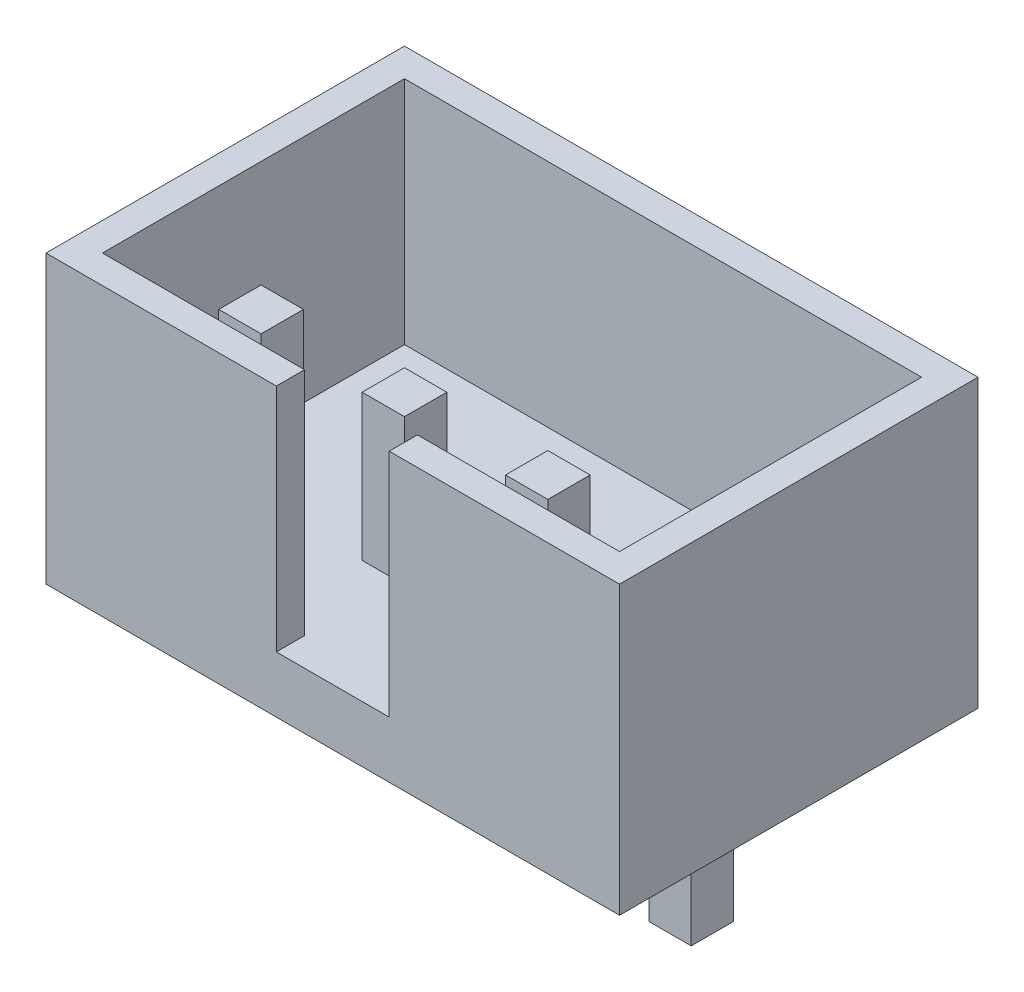
SolidWorks part; units mm, degrees
ref_plane "前视基准面" through (0, 0, 0) normal (0, 0, 1) x (1, 0, 0)
ref_plane "上视基准面" through (0, 0, 0) normal (0, 1, 0) x (1, 0, 0)
ref_plane "右视基准面" through (0, 0, 0) normal (1, 0, 0) x (0, 0, -1)
sketch "草图1" plane through (0, 0, 0) normal (0, 1, 0) x (1, 0, 0)
  line L0 (0, 7.1914) -> (0, -5.4429) construction
  line L1 (-5.08, 3.175) -> (5.08, 3.175)
  line L2 (-5.08, 3.175) -> (-5.08, -3.175)
  line L3 (-5.08, -3.175) -> (5.08, -3.175)
  line L4 (5.08, 3.175) -> (5.08, -3.175)
  line L5 (-10.6234, 0) -> (16.1963, 0) construction
  dimension "D1" = 10.16
  dimension "D2" = 6.35
extrude "拉伸1" add sketch "草图1" along normal blind 5.08
sketch "草图2" plane through (0, 5.08, 0) normal (0, 1, 0) x (-1, 0, 0)
  line L8 (4.58, -2.675) -> (4.58, 2.675)
  line L9 (4.58, 2.675) -> (-4.58, 2.675)
  line L10 (-4.58, 2.675) -> (-4.58, -2.675)
  line L11 (-4.58, -2.675) -> (4.58, -2.675)
  line L12 (4.58, -2.675) -> (4.58, 2.675)
  line L13 (4.58, 2.675) -> (-4.58, 2.675)
  line L14 (-4.58, 2.675) -> (-4.58, -2.675)
  line L15 (-4.58, -2.675) -> (4.58, -2.675)
  dimension "D1" = 0.5
extrude "切除-拉伸1" cut sketch "草图2" against normal offset from surface (4.08 mm away) 1 up to face at (0, 0, 0)
sketch "草图3" plane through (0, 0, 3.175) normal (0, 0, 1) x (1, 0, 0)
  line L0 (-5.08, 5.08) -> (5.08, 5.08) construction
  line L1 (-1, 5.08) -> (1, 5.08)
  line L2 (-1, 5.08) -> (-1, 1)
  line L3 (-1, 1) -> (1, 1)
  line L4 (1, 5.08) -> (1, 1)
  line L5 (4.58, 1) -> (-4.58, 1) construction
  line L6 (0, -1.5083) -> (0, 12.2426) construction
  dimension "D1" = 2
extrude "切除-拉伸2" cut sketch "草图3" against normal blind 1
sketch "草图4" plane through (0, 0, 0) normal (0, -1, 0) x (1, 0, 0)
  line L0 (7.6775, 0.635) -> (-8.5467, 0.635) construction
  line L1 (-5.08, 3.175) -> (5.08, 3.175) construction
  line L2 (0, -3.6953) -> (0, 4.0669) construction
  line L3 (-1.27, 2.1009) -> (-1.27, -0.7012) construction
  line L4 (-1.645, 1.01) -> (-0.895, 1.01)
  line L5 (-1.645, 1.01) -> (-1.645, 0.26)
  line L6 (-1.645, 0.26) -> (-0.895, 0.26)
  line L7 (-0.895, 1.01) -> (-0.895, 0.26)
  line L8 (0.895, 1.01) -> (1.645, 1.01)
  line L9 (0.895, 1.01) -> (0.895, 0.26)
  line L10 (0.895, 0.26) -> (1.645, 0.26)
  line L11 (1.645, 1.01) -> (1.645, 0.26)
  line L12 (3.435, 1.01) -> (4.185, 1.01)
  line L13 (3.435, 1.01) -> (3.435, 0.26)
  line L14 (3.435, 0.26) -> (4.185, 0.26)
  line L15 (4.185, 1.01) -> (4.185, 0.26)
  line L16 (-4.185, 1.01) -> (-3.435, 1.01)
  line L17 (-4.185, 1.01) -> (-4.185, 0.26)
  line L18 (-4.185, 0.26) -> (-3.435, 0.26)
  line L19 (-3.435, 1.01) -> (-3.435, 0.26)
  dimension "D1" = 2.54
  dimension "D2" = 0.75
  dimension "D3" = 0.75
  dimension "D4" = 1.27
extrude "拉伸2" add sketch "草图4" along normal blind 2 and the other way offset from surface 1.5 other way up to face at (0, 5.08, 0.975)
